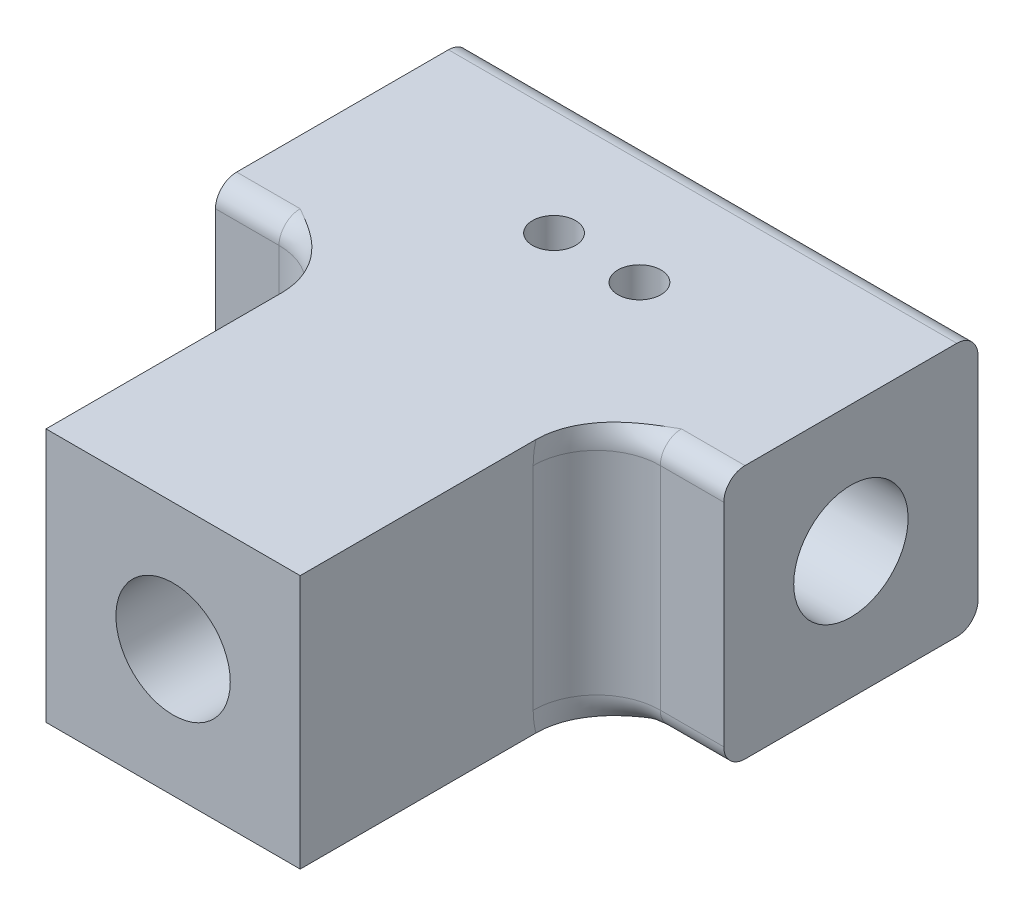
SolidWorks part; units mm, degrees
ref_plane "Front Plane" through (0, 0, 0) normal (0, 0, 1) x (1, 0, 0)
ref_plane "Top Plane" through (0, 0, 0) normal (0, 1, 0) x (1, 0, 0)
ref_plane "Right Plane" through (0, 0, 0) normal (1, 0, 0) x (0, 0, -1)
sketch "Sketch1" plane through (0, 0, 0) normal (0, 1, 0) x (1, 0, 0)
  line L3 (-6, -3) -> (6, -3)
  line L4 (-6, -3) -> (-6, 3)
  line L5 (-6, 3) -> (6, 3)
  line L6 (6, -3) -> (6, 3)
  line L7 (-6, -3) -> (6, 3) construction
  line L8 (-6, 3) -> (6, -3) construction
  point P0 (0, 0)
  dimension "D1" = 12
  dimension "D2" = 6
extrude "Boss-Extrude1" add sketch "Sketch1" along normal blind 6
sketch "Sketch2" plane through (0, 6, 0) normal (0, 1, 0) x (1, 0, 0)
  line L0 (-3.3, 0) -> (3.3, 0) construction
  line L1 (1.008, 0) -> (-1.008, 0)
  line L2 (0, -3.3) -> (0, 3.3) construction
  point P0 (1.008, 0)
  point P1 (-1.008, 0)
  point P7 (0, 0)
  dimension "D1" = 2.016
sketch "Sketch6" plane through (-6, 0, 0) normal (-1, 0, 0) x (0, 0, 1)
  line L0 (0, -55) -> (0, 55) construction
  line L1 (-3, 6) -> (3, 6) construction
  point P0 (0, 4.5)
  dimension "D1" = 1.5
hole_wizard "#60 (0.04) Diameter Hole1" positions "Sketch9" profile "Sketch10" hole size "#60" standard "ANSI Inch" end condition through all
sketch "Sketch9" plane through (0, 6, 0) normal (0, 1, 0) x (1, 0, 0)
  point P0 (1.008, 0)
  point P3 (-1.008, 0)
sketch "Sketch10" plane through (1.008, 6, 0) normal (1, 0, 0) x (0, 0, 1)
  line L0 (0, 0) -> (0, 6)
  line L1 (0, 6) -> (0.508, 6)
  line L2 (0.508, 6) -> (0.508, 0)
  line L5 (0.508, 0) -> (0, 0)
  line L11 (0, -6.35) -> (0, 107.95) construction
  dimension "Thru Hole Dia." = 1.016
  dimension "Thru Hole Depth" = 6
hole_wizard "Tap Drill for M2x0.4 Tap1" [suppressed] positions "Sketch7" profile "Sketch8" hole size "M2x0.4" standard "ANSI Metric"
sketch "Sketch7" [suppressed] plane through (-5, 0, 0) normal (-1, 0, 0) x (0, 0, 1)
  point P0 (0, 1.5)
sketch "Sketch8" [suppressed] plane through (-5, 1.5, 0) normal (0, 1, 0) x (0, 0, 1)
  line L0 (0, 0) -> (0, 4.85)
  line L1 (0, 4.85) -> (0.8, 4.3693)
  line L2 (0.8, 4.3693) -> (0.8, 0)
  line L5 (0.8, 0) -> (0, 0)
  line L10 (0, 4.85) -> (-0.8, 4.3693) construction
  line L11 (0, -6.35) -> (0, 107.95) construction
  dimension "Hole Dia." = 1.6
  dimension "Hole Depth" = 4.85
  dimension "Drill Angle" = 118
mirror "Mirror1" [suppressed] about plane through (0, 0, 0) normal (1, 0, 0)
sketch "Sketch15" plane through (0, 0, 3) normal (0, 0, 1) x (1, 0, 0)
  line L0 (0, -3.3) -> (0, 3.3) construction
  line L1 (-3, 0) -> (3, 0)
  line L2 (-3, 0) -> (-3, 6)
  line L3 (-3, 6) -> (3, 6)
  line L4 (3, 0) -> (3, 6)
  line L5 (-3, 0) -> (3, 6) construction
  line L6 (-3, 6) -> (3, 0) construction
  line L7 (-6, 6) -> (6, 6) construction
  point P0 (0, 3)
  dimension "D1" = 6
  dimension "D2" = 6
extrude "Boss-Extrude2" add sketch "Sketch15" along normal blind 7
sketch "Sketch16" plane through (0, 0, 10) normal (0, 0, 1) x (1, 0, 0)
  line L0 (0, -3.3) -> (0, 3.3) construction
  line L1 (3, 6) -> (-3, 6) construction
  circle A0 centre (0, 3) radius 1.35
  point P0 (0, 3)
  dimension "D2" = 2.7
  dimension "D1" = 3
hole_wizard "M2x0.4 Tapped Hole1" [suppressed] positions "Sketch17" profile "Sketch18" tap size "M2x0.4" standard "ANSI Metric"
sketch "Sketch17" [suppressed] plane through (0, 0, 8.5) normal (0, 0, 1) x (1, 0, 0)
  point P0 (0, 1.5)
sketch "Sketch18" [suppressed] plane through (0, 1.5, 8.5) normal (1, 0, 0) x (0, -1, 0)
  line L0 (0, 0) -> (0, 5.4807)
  line L1 (0, 5.4807) -> (0.8, 5)
  line L2 (0.8, 5) -> (0.8, 0)
  line L5 (0.8, 0) -> (0, 0)
  line L10 (0, 5.4807) -> (-0.8, 5) construction
  line L11 (0, -6.35) -> (0, 107.95) construction
  dimension "Tap Drill Dia." = 1.6
  dimension "Tap Drill Depth" = 5
  dimension "Drill Angle" = 118
cosmetic thread "Hole Thread1" [suppressed] parameters "D1"=4, "D2"=2
fillet "Fillet4" radius 0.5 6 edges at (4.5, 6, 3) (4.5, 0, 3) (-4.5, 0, 3) (0, 0, -3) (0, 6, -3) (-4.5, 6, 3)
fillet "Fillet3" radius 1.5 6 edges at (-3, 3, 3) (3, 3, 3) (-3, 5.8536, 2.8536) (-3, 0.1464, 2.8536) (3, 0.1464, 2.8536) (3, 5.8536, 2.8536)
sketch "Sketch19" plane through (-6, 0, 0) normal (-1, 0, 0) x (0, 0, 1)
  line L0 (0, -3.3) -> (0, 3.3) construction
  line L1 (-2.5, 6) -> (2.5, 6) construction
  circle A0 centre (0, 3) radius 1.35
  dimension "D1" = 2.7
  dimension "D2" = 3
extrude "Cut-Extrude1" cut sketch "Sketch19" against normal blind 5.5 contours A0
extrude "Cut-Extrude2" cut sketch "Sketch16" against normal blind 5 contours A0
mirror "Mirror2" about plane through (0, 0, 0) normal (1, 0, 0) of "Cut-Extrude1"
